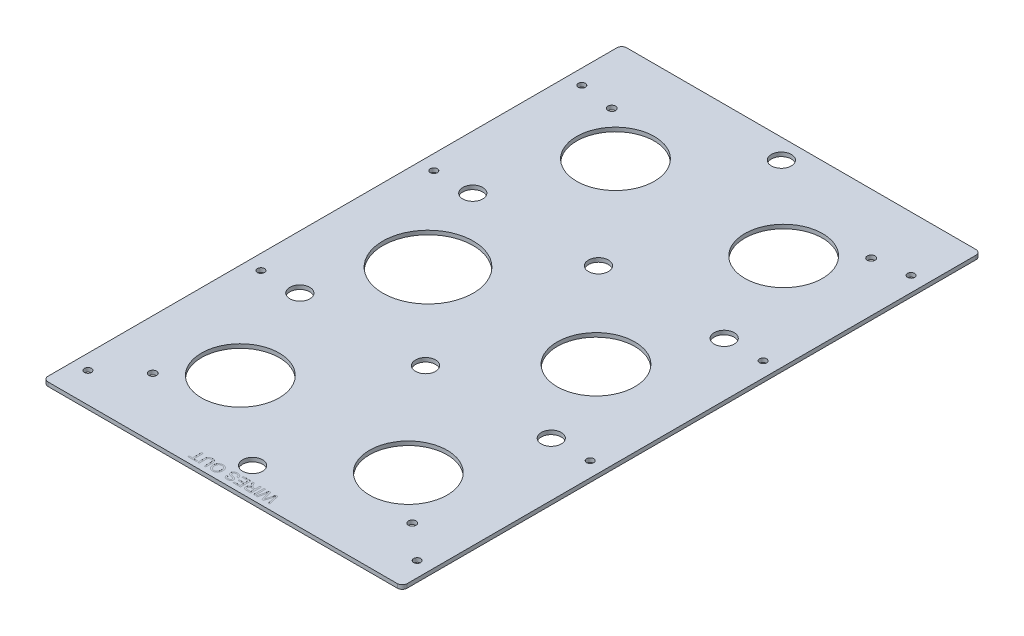
SolidWorks part; units mm, degrees
ref_plane "Front" through (0, 0, 0) normal (0, 0, 1) x (1, 0, 0)
ref_plane "Top" through (0, 0, 0) normal (0, 1, 0) x (1, 0, 0)
ref_plane "Right" through (0, 0, 0) normal (1, 0, 0) x (0, 0, -1)
sketch "Sketch1" plane through (0, 0, 0) normal (0, 1, 0) x (1, 0, 0)
  line L0 (-76.7713, -421.1347) -> (-76.8983, -421.1347) construction
  line L1 (-109.7785, -117.6047) -> (112.4715, -117.6047)
  line L2 (-112.9535, -120.7797) -> (-112.9535, -482.7297)
  line L3 (-109.7785, -485.9047) -> (112.4715, -485.9047)
  line L4 (115.6465, -120.7797) -> (115.6465, -482.7297)
  line L5 (-112.9535, -117.6047) -> (115.6465, -485.9047) construction
  line L6 (-112.9535, -485.9047) -> (115.6465, -117.6047) construction
  line L7 (-71.7672, -281.6904) -> (-32.5753, -321.6904) construction
  line L8 (28.334, -485.9047) -> (112.4715, -485.9047) construction
  line L9 (115.6465, -482.7297) -> (115.6465, -120.7797) construction
  circle A0 centre (54.8643, -421.2633) radius 24.727
  circle A1 centre (54.8643, -301.819) radius 24.727
  circle A2 centre (-52.1713, -421.1347) radius 24.727
  circle A4 centre (-52.1713, -182.3747) radius 24.727
  circle A5 centre (54.8643, -182.3747) radius 24.727
  arc A6 (-27.7828, -424.3536) -> (-74.4246, -410.6491) centre (-52.1713, -421.1347) ccw construction
  arc A7 (-27.7828, -424.3536) -> (-76.5598, -417.9159) centre (-52.1713, -421.1347) ccw construction
  arc A8 (115.6465, -120.7797) -> (112.4715, -117.6047) centre (112.4715, -120.7797) ccw
  arc A9 (-112.9535, -120.7797) -> (-109.7785, -117.6047) centre (-109.7785, -120.7797) cw
  arc A10 (-112.9535, -482.7297) -> (-109.7785, -485.9047) centre (-109.7785, -482.7297) ccw
  arc A11 (112.4715, -485.9047) -> (115.6465, -482.7297) centre (112.4715, -482.7297) ccw
  circle A12 centre (-52.1713, -301.6904) radius 28.7693
  circle A13 centre (-78.6635, -356.7838) radius 2.2479 construction
  circle A14 centre (-78.6635, -356.7838) radius 2.2479 construction
  circle A15 centre (1.3465, -356.7881) radius 2.2479 construction
  circle A16 centre (1.3465, -356.7881) radius 2.2479 construction
  circle A17 centre (81.3565, -356.7838) radius 2.2479 construction
  circle A18 centre (81.3565, -356.7838) radius 2.2479 construction
  circle A19 centre (81.3565, -246.7256) radius 2.2479 construction
  circle A20 centre (81.3565, -246.7256) radius 2.2479 construction
  circle A21 centre (1.3465, -246.7214) radius 2.2479 construction
  circle A22 centre (1.3465, -246.7214) radius 2.2479 construction
  circle A23 centre (-78.6635, -246.7256) radius 2.2479 construction
  circle A24 centre (-78.6635, -246.7256) radius 2.2479 construction
  circle A25 centre (1.3465, -130.3047) radius 2.2479 construction
  circle A26 centre (1.3465, -130.3047) radius 2.2479 construction
  circle A27 centre (1.3465, -466.8547) radius 2.2479 construction
  circle A28 centre (1.3465, -466.8547) radius 2.2479 construction
  circle A29 centre (1.3465, -466.8547) radius 6.35
  circle A30 centre (81.3565, -356.7838) radius 6.35
  circle A31 centre (1.3465, -356.7881) radius 6.35
  circle A32 centre (-78.6635, -356.7838) radius 6.35
  circle A33 centre (81.3565, -246.7256) radius 6.35
  circle A34 centre (1.3465, -246.7214) radius 6.35
  circle A35 centre (-78.6635, -246.7256) radius 6.35
  circle A36 centre (1.3465, -130.3047) radius 6.35
  circle A37 centre (83.8965, -155.7047) radius 2.4575 construction
  circle A38 centre (83.8965, -155.7047) radius 2.4575
  circle A39 centre (-81.2035, -155.7047) radius 2.4575 construction
  circle A40 centre (-81.2035, -155.7047) radius 2.4575
  circle A41 centre (-81.2035, -447.8047) radius 2.4575 construction
  circle A42 centre (-81.2035, -447.8047) radius 2.4575
  circle A43 centre (83.8965, -447.8047) radius 2.4575 construction
  circle A44 centre (83.8965, -447.8047) radius 2.4575
  circle A45 centre (-103.4285, -152.5297) radius 2.2479 construction
  circle A46 centre (-103.4285, -152.5297) radius 2.2479
  circle A47 centre (-103.4285, -246.7214) radius 2.2479 construction
  circle A48 centre (-103.4285, -246.7214) radius 2.2479
  circle A49 centre (106.1215, -152.5297) radius 2.2479 construction
  circle A50 centre (106.1215, -152.5297) radius 2.2479
  circle A51 centre (106.1215, -246.7214) radius 2.2479 construction
  circle A52 centre (106.1215, -246.7214) radius 2.2479
  circle A53 centre (106.1215, -356.7881) radius 2.2479 construction
  circle A54 centre (106.1215, -356.7881) radius 2.2479
  circle A55 centre (-103.4285, -356.7881) radius 2.2479 construction
  circle A56 centre (-103.4285, -356.7881) radius 2.2479
  circle A57 centre (-103.4285, -466.8547) radius 2.2479 construction
  circle A58 centre (-103.4285, -466.8547) radius 2.2479
  circle A59 centre (106.1215, -466.8547) radius 2.2479 construction
  circle A60 centre (106.1215, -466.8547) radius 2.2479
  point P0 (1.3465, -301.7547)
  point P5 (455.0963, -355.1939)
  point P81 (0, 0)
  point P82 (0, 0)
  point P83 (343.9713, -171.0439)
  dimension "D3" = 0.127
  dimension "D4" = 3.175
  dimension "D5" = 12.7
  dimension "D1" = 228.6
  dimension "D2" = 368.3
extrude "Boss-Extrude1" add sketch "Sketch1" along normal blind 2.54
sketch "Sketch2" plane through (0, 2.54, 0) normal (0, 1, 0) x (1, 0, 0)
  line L0 (28.1392, -475.9047) -> (28.1392, -485.9047) construction
  line L2 (28.1392, -475.9047) -> (-22.6608, -475.9047) construction
  line L3 (-109.7785, -485.9047) -> (112.4715, -485.9047) construction
  line L4 (115.6465, -482.7297) -> (115.6465, -120.7797) construction
  text T0 "WIRES OUT" font "Arial" height in points 26
  point P0 (28.1392, -475.9047)
  dimension "D1" = 10
  dimension "D2" = 50.8
  dimension "D3" = 87.5074
extrude "Cut-Extrude2" cut sketch "Sketch2" against normal blind 0.0254
